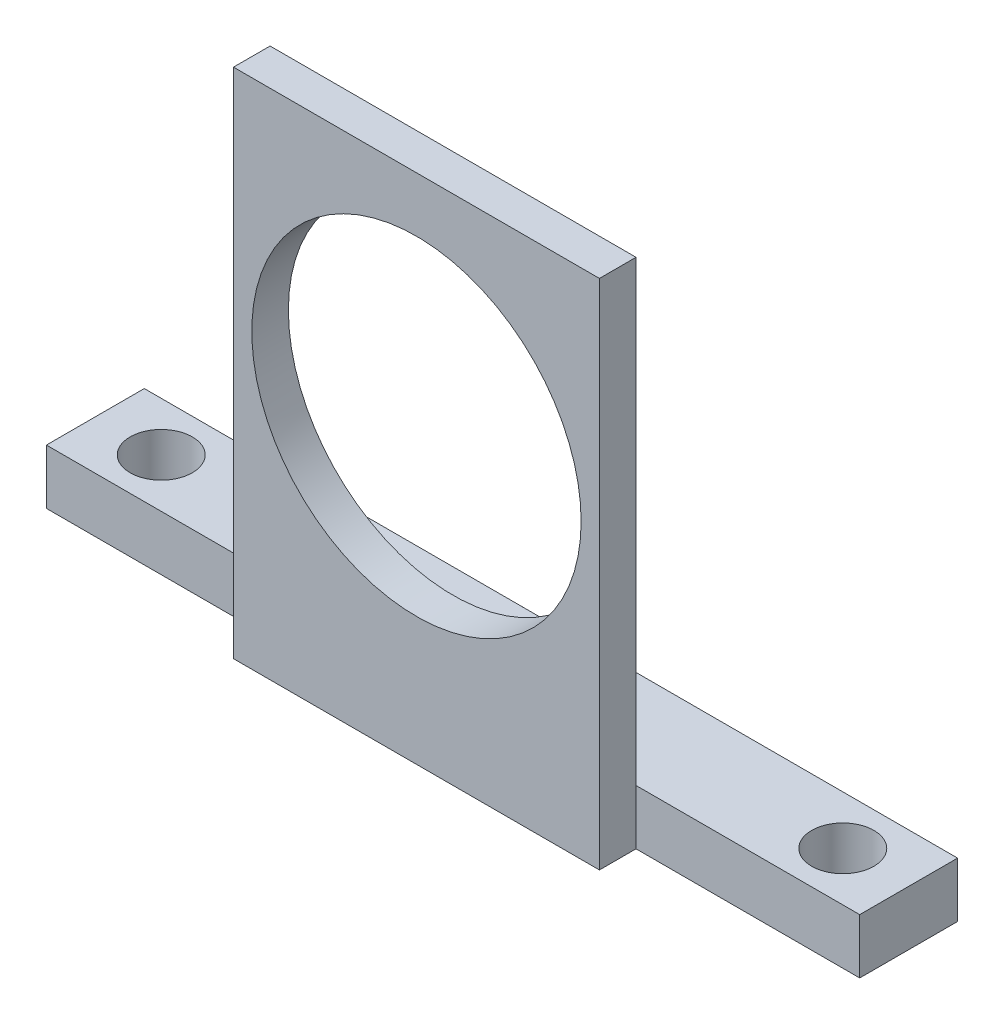
SolidWorks part; units mm, degrees
other "Markup1"
sketch "Sketch11" plane through (22.225, 12.5, -5.35) normal (0.6795, 0.6462, -0.3475) x (-0.117, -0.3721, -0.9208)
ref_plane "Front Plane" through (0, 0, 0) normal (0, 0, 1) x (1, 0, 0)
ref_plane "Top Plane" through (0, 0, 0) normal (0, 1, 0) x (1, 0, 0)
ref_plane "Right Plane" through (0, 0, 0) normal (1, 0, 0) x (0, 0, -1)
sketch "Sketch1" plane through (0, 0, 0) normal (0, 0, 1) x (1, 0, 0)
  line L1 (-10, -12.5) -> (10, -12.5)
  line L2 (-10, -12.5) -> (-10, 12.5)
  line L3 (-10, 12.5) -> (10, 12.5)
  line L4 (10, -12.5) -> (10, 12.5)
  line L5 (-10, -12.5) -> (10, 12.5) construction
  line L6 (-10, 12.5) -> (10, -12.5) construction
  point P0 (0, 0)
  dimension "D1" = 20
  dimension "D2" = 25
extrude "Boss-Extrude1" add sketch "Sketch1" along normal blind 2
sketch "Sketch2" plane through (0, -12.5, 0) normal (0, -1, 0) x (1, 0, 0)
  line L0 (-10, 2) -> (-10, 0) construction
  line L1 (-10, -5.35) -> (10, -5.35)
  line L2 (-10, -5.35) -> (-10, 7.35)
  line L3 (-10, 7.35) -> (10, 7.35)
  line L4 (10, -5.35) -> (10, 7.35)
  line L5 (-10, -5.35) -> (10, 7.35) construction
  line L6 (-10, 7.35) -> (10, -5.35) construction
  point P0 (0, 1)
  point P8 (-10, 1)
  dimension "D1" = 20
  dimension "D2" = 12.7
extrude "Boss-Extrude2" add sketch "Sketch2" along normal blind 3
sketch "Sketch3" plane through (0, -12.5, 0) normal (0, 1, 0) x (1, 0, 0)
sketch "Sketch5" plane through (0, -12.5, 0) normal (0, 1, 0) x (1, 0, 0)
sketch "Sketch6" plane through (0, -12.5, 0) normal (0, 1, 0) x (1, 0, 0)
  line L0 (-5.715, 2.7395) -> (5.715, 2.7395) construction
  point P0 (-5.715, 2.7395)
  point P3 (5.715, 2.7395)
  point P11 (0, 2.7395)
  dimension "D1" = 11.43
hole_wizard "M3 Clearance Hole1" positions "Sketch6" profile "Sketch4" hole size "M3" standard "ANSI Metric" end condition up to next
sketch "Sketch4" plane through (-5.715, -12.5, -2.7395) normal (1, 0, 0) x (0, 0, 1)
  line L0 (0, 0) -> (0, 3)
  line L1 (0, 3) -> (1.7, 3)
  line L2 (1.7, 3) -> (1.7, 0)
  line L5 (1.7, 0) -> (0, 0)
  line L11 (0, -6.35) -> (0, 107.95) construction
  dimension "Thru Hole Dia." = 3.4
  dimension "Thru Hole Depth" = 3
sketch "Sketch7" plane through (0, 0, 2) normal (0, 0, 1) x (1, 0, 0)
  line L0 (10, 12.5) -> (-10, 12.5) construction
  circle A0 centre (0, 0.5) radius 9
  dimension "D2" = 18
  dimension "D1" = 12
extrude "Cut-Extrude1" cut sketch "Sketch7" against normal through all
sketch "Sketch8" plane through (0, -12.5, 0) normal (0, 1, 0) x (1, 0, 0)
  line L1 (10, -7.35) -> (-10, -7.35)
  line L2 (10, -7.35) -> (10, -2)
  line L3 (10, -2) -> (-10, -2)
  line L4 (-10, -7.35) -> (-10, -2)
extrude "Cut-Extrude2" cut sketch "Sketch8" against normal through all
sketch "Sketch10" plane through (0, 0, -5.35) normal (0, 0, -1) x (-1, 0, 0)
  line L0 (-10, -12.5) -> (10, -12.5)
  line L1 (-22.225, -12.5) -> (22.225, -12.5)
  line L3 (-10, -15.5) -> (-22.225, -15.5)
  line L4 (-10, -15.5) -> (-10, -12.5)
  line L5 (-10, -12.5) -> (-22.225, -12.5)
  line L6 (-22.225, -15.5) -> (-22.225, -12.5)
  line L7 (10, -15.5) -> (22.225, -15.5)
  line L8 (10, -15.5) -> (10, -12.5)
  line L9 (10, -12.5) -> (22.225, -12.5)
  line L10 (22.225, -15.5) -> (22.225, -12.5)
  point P6 (0, -12.5)
  point P7 (0, -12.5)
  line M5 (-10, -12.5) -> (-10, -15.5)
  line M7 (10, -15.5) -> (10, -12.5)
  dimension "D1" = 44.45
extrude "Boss-Extrude3" add sketch "Sketch10" against normal blind 5.35 contours L6 L3 L1 M5 | L7 L10 L1 M7 region at (-16.1125, -14, -5.35) region at (16.1125, -14, -5.35)
sketch "Sketch13" plane through (0, -12.5, 0) normal (0, 1, 0) x (1, 0, 0)
  circle A0 centre (-5.715, 2.7395) radius 1.7
  circle A1 centre (5.715, 2.7395) radius 1.7
  dimension "D1" = 3.4
  dimension "D2" = 3.4
extrude "Boss-Extrude4" add sketch "Sketch13" against normal through all
sketch "Sketch15" plane through (0, -12.5, 0) normal (0, 1, 0) x (1, 0, 0)
  line L1 (-22.225, 0) -> (-22.225, 5.35) construction
  line L2 (22.225, 0) -> (22.225, 5.35) construction
  circle A0 centre (-18.625, 2.675) radius 1.7
  circle A1 centre (18.625, 2.675) radius 1.7
  point P4 (0, 0)
  point P6 (0, 0)
  point P9 (-22.225, 2.675)
  point P11 (22.225, 2.675)
  dimension "D1" = 3.4
  dimension "D2" = 3.4
  dimension "D3" = 3.6
  dimension "D5" = 37.25
extrude "Cut-Extrude3" cut sketch "Sketch15" along normal through all and the other way through all
